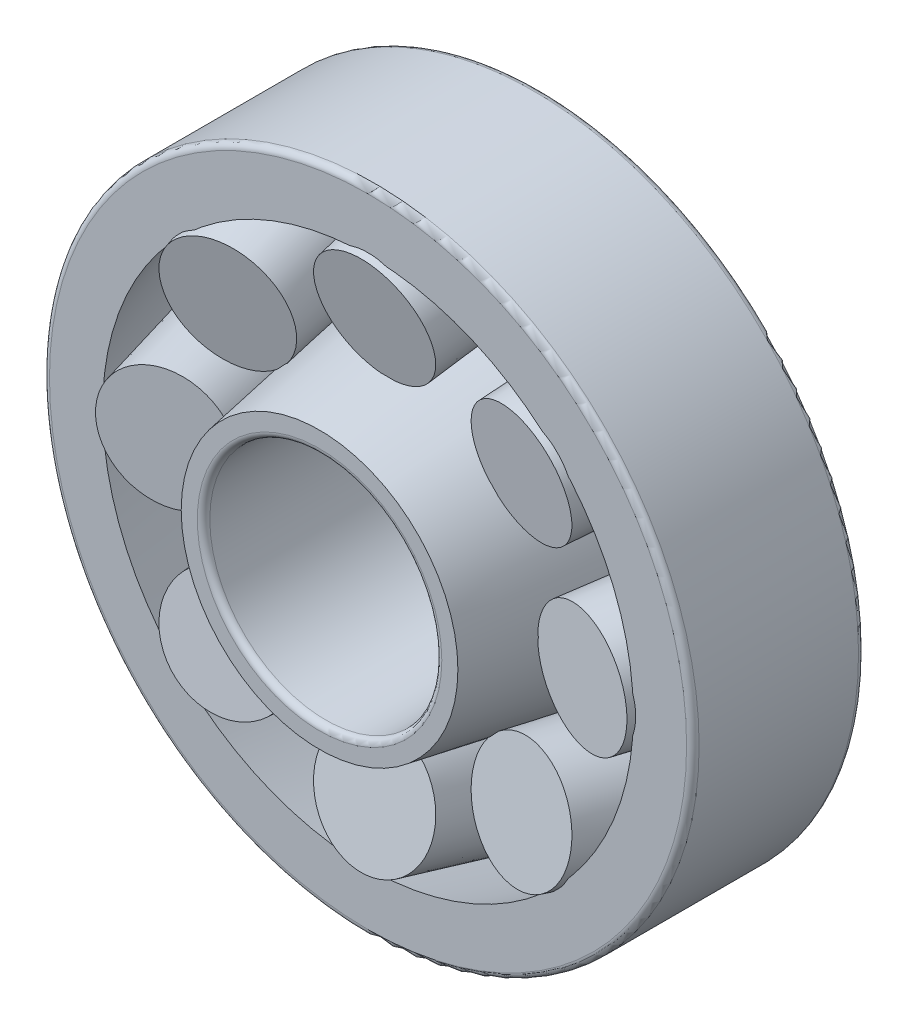
SolidWorks part; units mm, degrees
ref_plane "Front Plane" through (0, 0, 0) normal (0, 0, 1) x (1, 0, 0)
ref_plane "Top Plane" through (0, 0, 0) normal (0, 1, 0) x (1, 0, 0)
ref_plane "Right Plane" through (0, 0, 0) normal (1, 0, 0) x (0, 0, -1)
sketch "S" plane through (0, 0, 0) normal (0, 0, 1) x (1, 0, 0)
  line L0 (-7.125, 0) -> (7.125, 0) construction
  circle A0 centre (0, 0) radius 7.5 construction
  circle A1 centre (0, 0) radius 21 construction
  circle A2 centre (0, 0) radius 10.2 construction
  circle A3 centre (0, 0) radius 18.3 construction
  dimension "ID" = 15
  dimension "OD" = 42
  dimension "IDa" = 20.4
  dimension "ODa" = 36.6
  dimension "B" = 14.25
ref_axis "Z" through (0, 0, -7.8375) along (0, 0, 1)
sketch "ConeS" plane through (0, 0, 0) normal (0, 1, 0) x (1, 0, 0)
  line L0 (7.5, -7.125) -> (8.9437, -7.125)
  line L1 (8.9437, -7.125) -> (11.2051, 5.7)
  line L2 (11.2051, 5.7) -> (7.5, 5.7)
  line L3 (7.5, 5.7) -> (7.5, -7.125)
  line L4 (0, -11.6875) -> (0, 11.6875) construction
  dimension "x0" = 7.5
  dimension "y0" = 7.125
  dimension "x1" = 8.9437
  dimension "x2" = 11.2051
  dimension "y2" = 5.7
revolve "Cone" add sketch "ConeS" angle 360 about L4
sketch "CupS" plane through (0, 0, 0) normal (0, 1, 0) x (1, 0, 0)
  line L0 (17.1559, -3.99) -> (21, -3.99)
  line L1 (21, -3.99) -> (21, 7.125)
  line L2 (21, 7.125) -> (20.3431, 7.125)
  line L3 (20.3431, 7.125) -> (17.1559, -3.99)
  line L4 (0, -11.6875) -> (0, 11.6875) construction
  dimension "x0" = 17.1559
  dimension "y0" = 3.99
  dimension "x1" = 21
  dimension "y2" = 7.125
  dimension "x3" = 20.3431
revolve "Cup" add sketch "CupS" angle 360 about L4
sketch "RollerS" plane through (0, 0, 0) normal (0, 1, 0) x (1, 0, 0)
  line L0 (13.4252, -3.5625) -> (17.1792, -4.4317)
  line L1 (17.1792, -4.4317) -> (19.6187, 4.0118)
  line L2 (19.6187, 4.0118) -> (15.4048, 4.9875)
  line L3 (15.4048, 4.9875) -> (13.4252, -3.5625)
  dimension "x0" = 13.4252
  dimension "y0" = 3.5625
  dimension "x1" = 17.1792
  dimension "y1" = 4.4317
  dimension "x2" = 19.6187
  dimension "y2" = 4.0118
  dimension "x3" = 15.4048
  dimension "y3" = 4.9875
revolve "Roller" add sketch "RollerS" angle 360 about L3
pattern_circular "RollersPattern" count 8 over 360 about axis through (0, 0, -7.8375) along (0, 0, 1) of bodies 103
fillet "F1" radius 0.405 2 edges at (21, 0, -7.125) (21, 0, 3.99)
fillet "F2" radius 0.405 2 edges at (7.5, 0, -5.7) (7.5, 0, 7.125)
equation "\"x0@ConeS\" = abs(0.5*\"ID@S\")"
equation "\"y0@ConeS\" = abs(-0.5*\"B@S\")"
equation "\"x1@ConeS\" = abs(0.5*\"IDa@S\"-0.088163*\"B@S\")"
equation "\"x2@ConeS\" = abs(0.5*\"IDa@S\"+0.070531*\"B@S\")"
equation "\"y2@ConeS\" = abs(0.4*\"B@S\")"
equation "\"x0@CupS\" = abs(0.5*\"ODa@S\"-0.080289*\"B@S\")"
equation "\"y0@CupS\" = abs(-0.28*\"B@S\")"
equation "\"x1@CupS\" = abs(0.5*\"OD@S\")"
equation "\"y2@CupS\" = abs(0.5*\"B@S\")"
equation "\"x3@CupS\" = abs(0.5*\"ODa@S\"+0.143373*\"B@S\")"
equation "\"x0@RollerS\" = abs(0.25*\"IDa@S\"+0.25*\"ODa@S\"-0.057884*\"B@S\")"
equation "\"y0@RollerS\" = abs(-0.25*\"B@S\")"
equation "\"x1@RollerS\" = abs(0.006443*\"IDa@S\"+0.493557*\"ODa@S\"-0.071331*\"B@S\")"
equation "\"y1@RollerS\" = abs(-0.246887*\"B@S\"-0.056392*\"ODa@S\"+0.056392*\"IDa@S\")"
equation "\"x2@RollerS\" = abs(0.006443*\"IDa@S\"+0.493557*\"ODa@S\"+0.099863*\"B@S\")"
equation "\"y2@RollerS\" = abs(0.345641*\"B@S\"-0.056392*\"ODa@S\"+0.056392*\"IDa@S\")"
equation "\"x3@RollerS\" = abs(0.25*\"IDa@S\"+0.25*\"ODa@S\"+0.081038*\"B@S\")"
equation "\"y3@RollerS\" = abs(0.35*\"B@S\")"
equation "\"N@RollersPattern\" = int(4.833*(0.25*\"IDa@S\"+0.25*\"ODa@S\")/(0.5*\"ODa@S\"-0.5*\"IDa@S\"))"
equation "\"r_min@F2\" = \"r_min@F1\""
